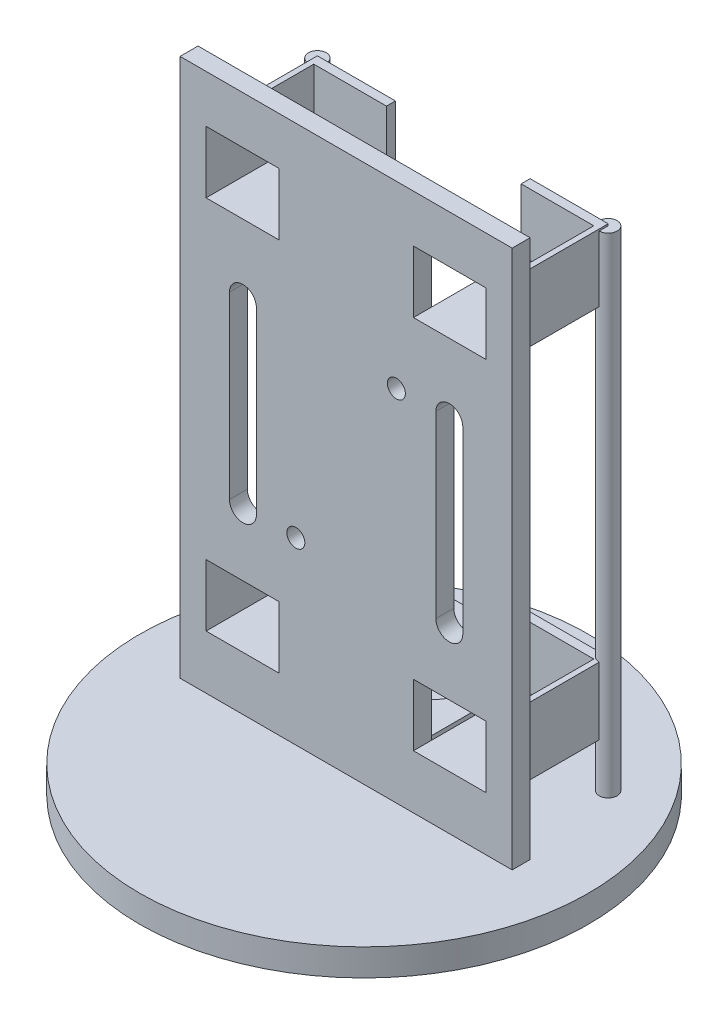
SolidWorks part; units mm, degrees
other "Markup1"
sketch "Sketch9" plane through (-63.5, 76.2, 63.5) normal (-0.9467, 0.1508, 0.2845) x (0.3097, 0.6687, 0.676)
sketch "Sketch10" plane through (-63.5, 76.2, 63.5) normal (-0.9467, 0.1508, 0.2845) x (0.3097, 0.6687, 0.676)
ref_plane "Front Plane" through (0, 0, 0) normal (0, 0, 1) x (1, 0, 0)
ref_plane "Top Plane" through (0, 0, 0) normal (0, 1, 0) x (1, 0, 0)
ref_plane "Right Plane" through (0, 0, 0) normal (1, 0, 0) x (0, 0, -1)
sketch "Sketch1" plane through (0, 0, 0) normal (0, 0, 1) x (1, 0, 0)
  line L1 (39.624, 45.212) -> (19.05, 45.212)
  line L2 (46.99, -76.2) -> (-46.99, -76.2)
  line L3 (46.99, -76.2) -> (46.99, 76.2)
  line L4 (46.99, 76.2) -> (-46.99, 76.2)
  line L5 (-46.99, -76.2) -> (-46.99, 76.2)
  line L6 (46.99, -76.2) -> (-46.99, 76.2) construction
  line L7 (46.99, 76.2) -> (-46.99, -76.2) construction
  line L8 (14.224, -25.4) -> (-14.224, -25.4) construction
  line L9 (14.224, -25.4) -> (14.224, 25.4) construction
  line L10 (14.224, 25.4) -> (-14.224, 25.4) construction
  line L11 (-14.224, -25.4) -> (-14.224, 25.4) construction
  line L12 (14.224, -25.4) -> (-14.224, 25.4) construction
  line L13 (14.224, 25.4) -> (-14.224, -25.4) construction
  line L14 (39.624, 45.212) -> (39.624, 62.738)
  line L15 (39.624, 62.738) -> (19.05, 62.738)
  line L16 (19.05, 45.212) -> (19.05, 62.738)
  line L17 (39.624, 45.212) -> (19.05, 62.738) construction
  line L18 (39.624, 62.738) -> (19.05, 45.212) construction
  line L19 (-39.624, -43.434) -> (-19.05, -43.434)
  line L20 (-39.624, -43.434) -> (-39.624, -60.96)
  line L21 (-39.624, -60.96) -> (-19.05, -60.96)
  line L22 (-19.05, -43.434) -> (-19.05, -60.96)
  line L23 (-39.624, -43.434) -> (-19.05, -60.96) construction
  line L24 (-39.624, -60.96) -> (-19.05, -43.434) construction
  line L25 (-19.05, 45.212) -> (-39.624, 45.212)
  line L26 (-19.05, 45.212) -> (-19.05, 62.738)
  line L27 (-19.05, 62.738) -> (-39.624, 62.738)
  line L28 (-39.624, 45.212) -> (-39.624, 62.738)
  line L29 (-19.05, 45.212) -> (-39.624, 62.738) construction
  line L30 (-19.05, 62.738) -> (-39.624, 45.212) construction
  line L31 (19.05, -43.434) -> (39.624, -43.434)
  line L32 (19.05, -43.434) -> (19.05, -60.96)
  line L33 (19.05, -60.96) -> (39.624, -60.96)
  line L34 (39.624, -43.434) -> (39.624, -60.96)
  line L35 (19.05, -43.434) -> (39.624, -60.96) construction
  line L36 (19.05, -60.96) -> (39.624, -43.434) construction
  line L38 (-33.02, -25.4) -> (-33.02, 25.4)
  line L40 (-25.4, -25.4) -> (-25.4, 25.4)
  line L41 (-33.02, -25.4) -> (-25.4, 25.4) construction
  line L42 (-33.02, 25.4) -> (-25.4, -25.4) construction
  line L45 (25.4, -25.4) -> (25.4, 25.4)
  line L47 (33.02, -25.4) -> (33.02, 25.4)
  line L48 (25.4, -25.4) -> (33.02, 25.4) construction
  line L49 (25.4, 25.4) -> (33.02, -25.4) construction
  circle A0 centre (-14.224, -25.4) radius 2.54
  circle A1 centre (14.224, 25.4) radius 2.54
  arc A2 (-33.02, 25.4) -> (-25.4, 25.4) centre (-29.21, 25.4) cw
  arc A3 (-25.4, -25.4) -> (-33.02, -25.4) centre (-29.21, -25.4) cw
  arc A4 (25.4, 25.4) -> (33.02, 25.4) centre (29.21, 25.4) cw
  arc A5 (33.02, -25.4) -> (25.4, -25.4) centre (29.21, -25.4) cw
  point P0 (0, 0)
  point P1 (0, 0)
  point P13 (29.337, 53.975)
  point P18 (-29.337, -52.197)
  point P23 (-29.337, 53.975)
  point P28 (29.337, -52.197)
  point P33 (-29.21, 0)
  point P39 (29.21, 0)
  dimension "D5" = 5.08
  dimension "D6" = 5.08
  dimension "D1" = 50.8
  dimension "D2" = 28.448
  dimension "D3" = 152.4
  dimension "D4" = 93.98
  dimension "D7" = 17.526
  dimension "D8" = 20.574
  dimension "D9" = 4.826
  dimension "D10" = 37.338
  dimension "D11" = 35.56
  dimension "D12" = 4.826
  dimension "D13" = 20.574
  dimension "D14" = 17.526
  dimension "D15" = 17.526
  dimension "D16" = 20.574
  dimension "D17" = 20.574
  dimension "D18" = 38.1
  dimension ".63" = 17.526
  dimension "D19" = 38.1
  dimension "D20" = 35.56
  dimension "D21" = 37.338
  dimension "D22" = 7.62
  dimension "D23" = 7.62
  dimension "D24" = 29.21
  dimension "D25" = 29.21
  dimension "D26" = 50.8
  dimension "D27" = 50.8
extrude "Boss-Extrude1" add sketch "Sketch1" along normal blind 5.08
sketch "Sketch3" plane through (0, 0, 0) normal (0, 0, -1) x (-1, 0, 0)
  line L9 (-19.05, 45.212) -> (-39.624, 45.212)
  line L10 (-39.624, 45.212) -> (-39.624, 62.738)
  line L11 (-39.624, 62.738) -> (-41.148, 62.738)
  line L12 (-19.05, 45.212) -> (-19.05, 43.688)
  line L13 (-19.05, -59.563) -> (-19.05, 59.563) construction
  line L14 (-41.148, 62.738) -> (-41.148, 43.688)
  line L15 (-19.05, 43.688) -> (-41.148, 43.688)
  line L16 (19.05, 45.212) -> (39.624, 45.212)
  line L17 (39.624, 45.212) -> (39.624, 62.738)
  line L18 (39.624, 62.738) -> (41.148, 62.738)
  line L19 (19.05, 45.212) -> (19.05, 43.688)
  line L20 (19.05, 59.563) -> (19.05, -59.563) construction
  line L21 (19.05, -60.96) -> (39.624, -60.96)
  line L22 (39.624, -60.96) -> (39.624, -43.434)
  line L23 (39.624, -43.434) -> (41.148, -43.434)
  line L24 (19.05, -60.96) -> (19.05, -62.484)
  line L25 (-39.624, -43.434) -> (-39.624, -60.96)
  line L26 (-39.624, -60.96) -> (-19.05, -60.96)
  line L27 (-19.05, -60.96) -> (-19.05, -62.484)
  line L28 (-39.624, -43.434) -> (-41.148, -43.434)
  line L29 (41.148, 62.738) -> (41.148, 43.688)
  line L30 (19.05, 43.688) -> (41.148, 43.688)
  line L31 (19.05, -62.484) -> (41.148, -62.484)
  line L32 (41.148, -43.434) -> (41.148, -62.484)
  line L33 (-19.05, -62.484) -> (-41.148, -62.484)
  line L34 (-41.148, -43.434) -> (-41.148, -62.484)
  dimension "D1" = 1.524
  dimension "D2" = 1.524
  dimension "D3" = 1.524
  dimension "D4" = 1.524
  dimension "D5" = 1.524
  dimension "D6" = 1.524
  dimension "D7" = 1.524
  dimension "D8" = 1.524
extrude "Boss-Extrude2" add sketch "Sketch3" along normal blind 27.94
sketch "Sketch4" plane through (0, 0, -27.94) normal (0, 0, -1) x (-1, 0, 0)
  line L1 (-41.148, 43.688) -> (-19.05, 43.688)
  line L2 (-41.148, 43.688) -> (-41.148, 62.738)
  line L3 (-41.148, 62.738) -> (-19.05, 62.738)
  line L4 (-19.05, 43.688) -> (-19.05, 62.738)
  line L5 (41.148, 43.688) -> (19.05, 43.688)
  line L6 (41.148, 43.688) -> (41.148, 62.738)
  line L7 (41.148, 62.738) -> (19.05, 62.738)
  line L8 (19.05, 43.688) -> (19.05, 62.738)
  line L9 (41.148, -62.484) -> (19.05, -62.484)
  line L10 (41.148, -62.484) -> (41.148, -43.434)
  line L11 (41.148, -43.434) -> (19.05, -43.434)
  line L12 (19.05, -62.484) -> (19.05, -43.434)
  line L14 (-41.148, -62.484) -> (-19.05, -62.484)
  line L15 (-41.148, -62.484) -> (-41.148, -43.434)
  line L16 (-41.148, -43.434) -> (-19.05, -43.434)
  line L17 (-19.05, -62.484) -> (-19.05, -43.434)
extrude "Boss-Extrude3" add sketch "Sketch4" against normal blind 2.54
sketch "Sketch5" plane through (0, -76.2, 0) normal (0, -1, 0) x (1, 0, 0)
  circle A0 centre (0, 0) radius 63.5
  dimension "D1" = 127
extrude "Boss-Extrude4" add sketch "Sketch5" along normal blind 7.62
sketch "Sketch6" plane through (0, -76.2, 0) normal (0, 1, 0) x (1, 0, 0)
  line L1 (-18.288, 37.338) -> (18.288, 37.338)
  line L2 (-18.288, 37.338) -> (-18.288, 0.762)
  line L3 (-18.288, 0.762) -> (18.288, 0.762)
  line L4 (18.288, 37.338) -> (18.288, 0.762)
  circle A0 centre (0, 19.05) radius 13.335
  dimension "D1" = 26.67
extrude "Boss-Extrude5" add sketch "Sketch6" along normal blind 15.621
sketch "Sketch8" plane through (0, -76.2, 0) normal (0, 1, 0) x (1, 0, 0)
  circle A0 centre (-41.148, 27.94) radius 2.54
  circle A1 centre (41.148, 27.94) radius 2.54
  dimension "D1" = 5.08
  dimension "D2" = 5.08
extrude "Boss-Extrude6" add sketch "Sketch8" along normal blind 138.43
